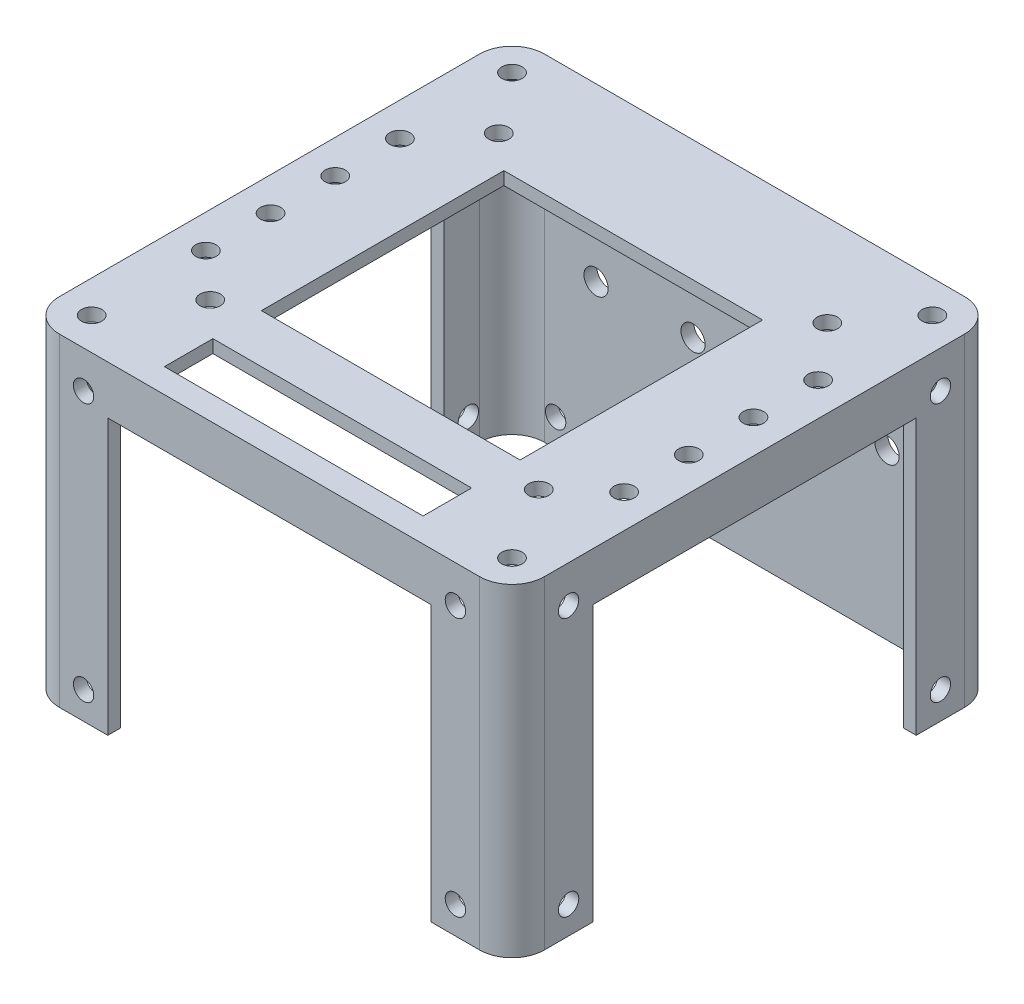
SolidWorks part; units mm, degrees
material "Custom Plastic"
ref_plane "Front Plane" through (0, 0, 0) normal (0, 0, 1) x (1, 0, 0)
ref_plane "Top Plane" through (0, 0, 0) normal (0, 1, 0) x (1, 0, 0)
ref_plane "Right Plane" through (0, 0, 0) normal (1, 0, 0) x (0, 0, -1)
sketch "Sketch1" plane through (0, 0, 0) normal (0, 1, 0) x (1, 0, 0)
  circle A2 centre (-50.8, 46.711) radius 3.15
  circle A3 centre (50.8, -42.532) radius 3.15
  circle A4 centre (-50.8, -42.532) radius 3.15
  circle A5 centre (50.8, 46.711) radius 3.15
sketch "Sketch9" plane through (0, 0, 0) normal (0, 1, 0) x (1, 0, 0)
  circle A0 centre (64.67, -30) radius 3.15
  circle A1 centre (-64.67, -30) radius 3.15
  circle A4 centre (64.67, -10) radius 3.15
  circle A5 centre (-64.67, -10) radius 3.15
  circle A6 centre (64.67, 10) radius 3.15
  circle A7 centre (-64.67, 10) radius 3.15
  circle A8 centre (64.67, 30) radius 3.15
  circle A9 centre (-64.67, 30) radius 3.15
  dimension "D1" = 4
extrude "Boss-Extrude10" add sketch "Sketch9" against normal mid plane 20 separate body
sketch "Sketch10" plane through (0, 0, 0) normal (0, 1, 0) x (1, 0, 0)
  line L1 (-40, 37.5) -> (40, 37.5)
  line L2 (-40, 37.5) -> (-40, -37.5)
  line L3 (-40, -37.5) -> (40, -37.5)
  line L4 (40, 37.5) -> (40, -37.5)
  line L5 (-40, 37.5) -> (40, -37.5) construction
  line L6 (-40, -37.5) -> (40, 37.5) construction
  point P0 (0, 0)
extrude "Boss-Extrude12" add sketch "Sketch10" against normal mid plane 20 separate body
sketch "Sketch15" plane through (0, 0, 0) normal (0, 1, 0) x (1, 0, 0)
  circle A2 centre (-50.8, 46.711) radius 3.15
  circle A3 centre (50.8, -42.532) radius 3.15
  circle A4 centre (-50.8, -42.532) radius 3.15
  circle A5 centre (50.8, 46.711) radius 3.15
extrude "Boss-Extrude17" add sketch "Sketch15" against normal mid plane 20 separate body
move or copy body "Body-Move/Copy4" bodies to move or copy 139 142 141 140 copy no translate (0, 1, 0)
sketch "Sketch22" plane through (0, 0, 0) normal (0, 1, 0) x (1, 0, 0)
  line L1 (-75, 75) -> (75, 75)
  line L2 (-75, 75) -> (-75, -75)
  line L3 (-75, -75) -> (75, -75)
  line L4 (75, 75) -> (75, -75)
  line L5 (-75, 75) -> (75, -75) construction
  line L6 (-75, -75) -> (75, 75) construction
  point P0 (0, 0)
extrude "Boss-Extrude19" add sketch "Sketch22" along normal blind 4 separate body
sketch "Sketch29" plane through (0, 4, 0) normal (0, 1, 0) x (1, 0, 0)
  line L1 (-75, 75) -> (75, 75)
  line L2 (-75, 75) -> (-75, -75)
  line L3 (-75, -75) -> (75, -75)
  line L4 (75, 75) -> (75, -75)
  line L5 (-75, 75) -> (75, -75) construction
  line L6 (-75, -75) -> (75, 75) construction
  line L7 (-71, 71) -> (71, 71)
  line L8 (-71, 71) -> (-71, -71)
  line L9 (-71, -71) -> (71, -71)
  line L10 (71, 71) -> (71, -71)
  line L11 (-71, 71) -> (71, -71) construction
  line L12 (-71, -71) -> (71, 71) construction
  point P0 (0, 0)
  point P5 (0, 0)
extrude "Boss-Extrude20" add sketch "Sketch29" against normal blind 100
fillet "Fillet12" radius 10 4 edges at (-75, -46, -75) (-75, -46, 75) (75, -46, 75) (75, -46, -75)
sketch "Sketch31" plane through (0, 4, 0) normal (0, 1, 0) x (1, 0, 0)
  line L5 (-71, 50) -> (-79, 50)
  line L6 (-71, 50) -> (-71, -50)
  line L11 (-71, -50) -> (-79, -50)
  line L12 (-79, 50) -> (-79, -50)
  line L13 (79, 50) -> (71, 50)
  line L14 (79, 50) -> (79, -50)
  line L15 (79, -50) -> (71, -50)
  line L16 (71, 50) -> (71, -50)
  line L17 (79, 50) -> (71, -50) construction
  line L18 (79, -50) -> (71, 50) construction
  line L19 (-71, 50) -> (-79, -50) construction
  line L20 (-71, -50) -> (-79, 50) construction
  line L29 (-65, -75) -> (65, -75) construction
  line L30 (-50, -71) -> (50, -71)
  line L31 (-50, -71) -> (-50, -79)
  line L32 (-50, -79) -> (50, -79)
  line L33 (50, -71) -> (50, -79)
  line L34 (-50, -71) -> (50, -79) construction
  line L35 (-50, -79) -> (50, -71) construction
  point P0 (-75, 0)
  point P11 (75, 0)
  point P21 (0, -75)
extrude "Boss-Extrude21" add sketch "Sketch31" against normal blind 100 separate body
move or copy body "Body-Move/Copy5" bodies to move or copy 155 158 156 copy no translate (0, -15, 0)
sketch "Sketch32" plane through (0, 0, 0) normal (0, 0, 1) x (1, 0, 0)
  circle A0 centre (57.5, -7.5) radius 3.15
  circle A1 centre (-57.5, -7.5) radius 3.15
  circle A2 centre (-57.5, -87.5) radius 3.15
  circle A3 centre (57.5, -87.5) radius 3.15
extrude "Boss-Extrude22" add sketch "Sketch32" along normal mid plane 150 separate body
sketch "Sketch34" plane through (75, 0, 0) normal (1, 0, 0) x (0, 0, -1)
  circle A0 centre (-57.5, -7.5) radius 3.15
  circle A1 centre (57.5, -7.5) radius 3.15
  circle A2 centre (-57.5, -87.5) radius 3.15
  circle A3 centre (57.5, -87.5) radius 3.15
extrude "Boss-Extrude23" add sketch "Sketch34" against normal blind 150 separate body
combine bodies "Combine4" operation type subtract main body 154 bodies to subtract 169 168 167 166 165 164 163 162 160 159 170
sketch "Sketch35" plane through (0, 0, 0) normal (0, 1, 0) x (1, 0, 0)
  circle A0 centre (65, -65) radius 3.15
  circle A1 centre (-65, 65) radius 3.15
  circle A2 centre (-65, -65) radius 3.15
  circle A3 centre (65, 65) radius 3.15
extrude "Boss-Extrude25" add sketch "Sketch35" against normal mid plane 20 separate body
fillet "Fillet13" radius 10 4 edges at (71, -48, 71) (-71, -48, 71) (-71, -48, -71) (71, -48, -71)
sketch "Sketch38" plane through (0, 0, 0) normal (0, 1, 0) x (1, 0, 0)
  line L1 (40, -67.5) -> (-40, -67.5)
  line L2 (40, -67.5) -> (40, -52.5)
  line L3 (40, -52.5) -> (-40, -52.5)
  line L4 (-40, -67.5) -> (-40, -52.5)
  line L5 (40, -67.5) -> (-40, -52.5) construction
  line L6 (40, -52.5) -> (-40, -67.5) construction
  point P0 (0, -60)
extrude "Boss-Extrude27" add sketch "Sketch38" along normal through all and the other way through all separate body
combine bodies "Combine12" operation type subtract main body 183 bodies to subtract 196 190 189 188 187
combine bodies "Combine13" operation type subtract main body 198 bodies to subtract 146 145 144 143 124 113 112
sketch "Sketch40" plane through (0, 0, 0) normal (0, 1, 0) x (1, 0, 0)
  line L0 (71, -61) -> (71, 61) construction
  line L1 (-61, -71) -> (61, -71) construction
  line L2 (71, -46) -> (46, -46)
  line L3 (71, -46) -> (71, -71)
  line L4 (71, -71) -> (46, -71)
  line L5 (46, -46) -> (46, -71)
  line L6 (61, 71) -> (-61, 71) construction
  line L7 (46, 71) -> (71, 71)
  line L8 (46, 71) -> (46, 46)
  line L9 (46, 46) -> (71, 46)
  line L10 (71, 71) -> (71, 46)
  line L11 (-71, 61) -> (-71, -61) construction
  line L12 (-71, 46) -> (-46, 46)
  line L13 (-71, 46) -> (-71, 71)
  line L14 (-71, 71) -> (-46, 71)
  line L15 (-46, 46) -> (-46, 71)
  line L17 (-71, -46) -> (-46, -46)
  line L18 (-71, -46) -> (-71, -71)
  line L19 (-71, -71) -> (-46, -71)
  line L20 (-46, -46) -> (-46, -71)
sketch "Sketch36" plane through (0, 0, 0) normal (0, 1, 0) x (1, 0, 0)
  line L0 (-46.5147, -46.5147) -> (-63.4853, -63.4853) construction
  line L2 (-40.1508, -52.8787) -> (-57.1213, -69.8492)
  line L6 (-46.5147, 46.5147) -> (-63.4853, 63.4853) construction
  line L9 (-52.8787, -40.1508) -> (-69.8492, -57.1213)
  line L12 (-52.8787, 40.1508) -> (-69.8492, 57.1213)
  line L13 (-40.1508, 52.8787) -> (-57.1213, 69.8492)
  line L14 (46.5147, -46.5147) -> (63.4853, -63.4853) construction
  line L15 (52.8787, -40.1508) -> (69.8492, -57.1213)
  line L16 (40.1508, -52.8787) -> (57.1213, -69.8492)
  line L17 (46.5147, 46.5147) -> (63.4853, 63.4853) construction
  line L18 (40.1508, 52.8787) -> (57.1213, 69.8492)
  line L19 (52.8787, 40.1508) -> (69.8492, 57.1213)
  arc A13 (-52.8787, 40.1508) -> (-40.1508, 52.8787) centre (-46.5147, 46.5147) ccw
  arc A14 (-57.1213, 69.8492) -> (-69.8492, 57.1213) centre (-63.4853, 63.4853) ccw
  arc A15 (-40.1508, -52.8787) -> (-52.8787, -40.1508) centre (-46.5147, -46.5147) ccw
  arc A16 (-69.8492, -57.1213) -> (-57.1213, -69.8492) centre (-63.4853, -63.4853) ccw
  arc A17 (52.8787, -40.1508) -> (40.1508, -52.8787) centre (46.5147, -46.5147) ccw
  arc A18 (57.1213, -69.8492) -> (69.8492, -57.1213) centre (63.4853, -63.4853) ccw
  arc A19 (40.1508, 52.8787) -> (52.8787, 40.1508) centre (46.5147, 46.5147) ccw
  arc A20 (69.8492, 57.1213) -> (57.1213, 69.8492) centre (63.4853, 63.4853) ccw
  point P2 (-55, 55)
  point P3 (-55, -55)
  point P12 (55, -55)
  point P19 (55, 55)
extrude "Boss-Extrude28" add sketch "Sketch36" against normal blind 3 separate body
extrude "Boss-Extrude31" add sketch "Sketch40" against normal blind 4.5 separate body
combine bodies "Combine15" operation type add bodies to combine 206 207 208 209 199
combine bodies "Combine16" operation type subtract main body 210 bodies to subtract 203 202 201 200
combine bodies "Combine17" operation type subtract main body 211 bodies to subtract 217 216 215 214 213 212
ref_plane "Plane2" through (0, 0, -75) normal (0, 0, -1) x (-1, 0, 0)
sketch "Sketch41" plane through (0, 0, -75) normal (0, 0, -1) x (-1, 0, 0)
  circle A0 centre (-45, -45) radius 3.75
  circle A1 centre (-15, -45) radius 3.75
  circle A2 centre (15, -45) radius 3.75
  circle A3 centre (45, -45) radius 3.75
  dimension "D1" = 4
extrude "Boss-Extrude32" add sketch "Sketch41" against normal through all separate body
combine bodies "Combine18" operation type subtract main body 218 bodies to subtract 221 220 219 222
fillet "Fillet14" radius 15 4 edges at (-46, -3.75, 46) (-46, -3.75, -46) (46, -3.75, -46) (46, -3.75, 46)
